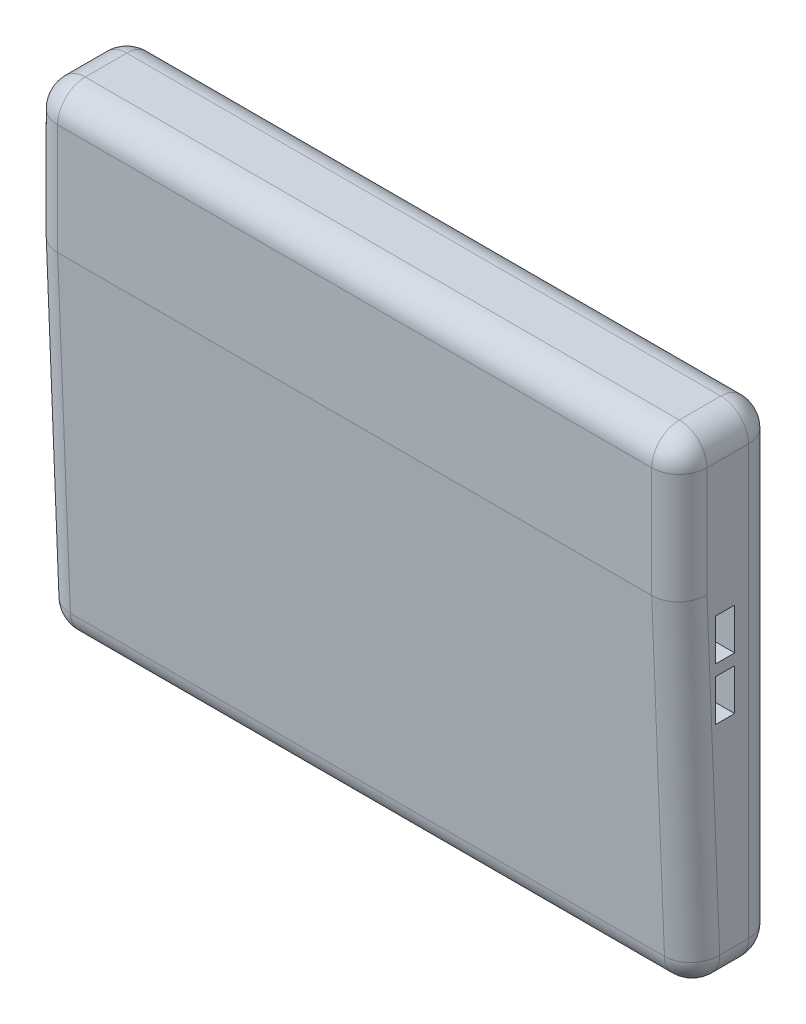
SolidWorks part; units mm, degrees
ref_plane "Plan de face" through (0, 0, 0) normal (0, 0, 1) x (1, 0, 0)
ref_plane "Plan de dessus" through (0, 0, 0) normal (0, 1, 0) x (1, 0, 0)
ref_plane "Plan de droite" through (0, 0, 0) normal (1, 0, 0) x (0, 0, -1)
sketch "Esquisse1" plane through (0, 0, 0) normal (0, 0, 1) x (1, 0, 0)
  line L1 (-32.2034, 29.3169) -> (182.7966, 29.3169)
  line L2 (-42.2034, 19.3169) -> (-42.2034, -135.6831)
  line L3 (-32.2034, -145.6831) -> (182.7966, -145.6831)
  line L4 (192.7966, 19.3169) -> (192.7966, -135.6831)
  arc A0 (-32.2034, 29.3169) -> (-42.2034, 19.3169) centre (-32.2034, 19.3169) ccw
  arc A1 (182.7966, 29.3169) -> (192.7966, 19.3169) centre (182.7966, 19.3169) cw
  arc A2 (-42.2034, -135.6831) -> (-32.2034, -145.6831) centre (-32.2034, -135.6831) ccw
  arc A3 (182.7966, -145.6831) -> (192.7966, -135.6831) centre (182.7966, -135.6831) ccw
  point P6 (-42.2034, 29.3169)
  point P9 (192.7966, 29.3169)
  point P12 (-42.2034, -145.6831)
  dimension "D3" = 10
  dimension "D4" = 10
  dimension "D1" = 235
  dimension "D2" = 175
extrude "Extrusion1" add sketch "Esquisse1" along normal blind 35
sketch "Esquisse5" plane through (192.7966, 0, 0) normal (1, 0, 0) x (0, 0, -1)
  line L0 (-35, -20.6831) -> (-35, -145.6831)
  line L3 (-35, -135.6831) -> (-35, 19.3169) construction
  line L4 (-35, -145.6831) -> (-30, -145.6831)
  line L7 (-30, -145.6831) -> (-35, -20.6831)
  line L8 (-35, 29.3169) -> (0, 29.3169) construction
  line L9 (-35, -145.6831) -> (0, -145.6831) construction
  dimension "D1" = 50
  dimension "D2" = 0
  dimension "D3" = 5
extrude "Extrusion7" cut sketch "Esquisse5" against normal through all
fillet "Congé1" [suppressed] radius 10
fillet "Congé2" radius 10 8 edges at (189.8677, 26.388, 0) (192.7966, -58.1831, 0) (189.8677, -142.7541, 0) (75.2966, -145.6831, 0) (-39.2744, -142.7541, 0) (-42.2034, -58.1831, 0) (-39.2744, 26.388, 0) (75.2966, 29.3169, 0)
sketch "Esquisse2" plane through (192.7966, 0, 0) normal (1, 0, 0) x (0, 0, -1)
  line L0 (-35, 29.3169) -> (-10, 29.3169) construction
  line L1 (-15, -28.6831) -> (-22, -28.6831)
  line L2 (-15, -28.6831) -> (-15, -43.6831)
  line L3 (-15, -43.6831) -> (-22, -43.6831)
  line L4 (-22, -28.6831) -> (-22, -43.6831)
  line L5 (-15, -47.6831) -> (-22, -47.6831)
  line L6 (-15, -47.6831) -> (-15, -62.6831)
  line L7 (-15, -62.6831) -> (-22, -62.6831)
  line L8 (-22, -47.6831) -> (-22, -62.6831)
  line L9 (0, 19.3169) -> (0, -135.6831) construction
  point P12 (0, -58.1831)
  dimension "D1" = 92
  dimension "D2" = 73
  dimension "D3" = 15
  dimension "D4" = 15
  dimension "D5" = 7
  dimension "D6" = 7
  dimension "D7" = 15
  dimension "D8" = 15
extrude "Extrusion2" cut sketch "Esquisse2" against normal blind 15
sketch "Esquisse3" plane through (-42.2034, 0, 0) normal (-1, 0, 0) x (0, 0, 1)
  line L0 (0, 19.3169) -> (0, -135.6831) construction
  line L1 (15, -50.6831) -> (22, -50.6831)
  line L2 (15, -50.6831) -> (15, -65.6831)
  line L3 (15, -65.6831) -> (22, -65.6831)
  line L4 (22, -50.6831) -> (22, -65.6831)
  line L5 (35, 29.3169) -> (10, 29.3169) construction
  line L6 (0, -135.6831) -> (0, 19.3169) construction
  line L7 (12, 7.3169) -> (22, 7.3169)
  line L8 (12, 7.3169) -> (12, -8.6831)
  line L9 (12, -8.6831) -> (22, -8.6831)
  line L10 (22, 7.3169) -> (22, -8.6831)
  dimension "D1" = 15
  dimension "D2" = 7
  dimension "D3" = 15
  dimension "D4" = 80
  dimension "D5" = 16
  dimension "D6" = 10
  dimension "D7" = 12
  dimension "D8" = 22
extrude "Extrusion3" cut sketch "Esquisse3" against normal blind 15
sketch "Esquisse4" plane through (0, 0, 0) normal (0, 0, -1) x (-1, 0, 0)
  line L0 (-75.2966, 19.3169) -> (-75.2966, -135.6831) construction
  line L1 (32.2034, 19.3169) -> (-182.7966, 19.3169) construction
  line L2 (-182.7966, -135.6831) -> (32.2034, -135.6831) construction
  line L3 (-182.7966, -58.1831) -> (32.2034, -58.1831) construction
  line L4 (-182.7966, 19.3169) -> (-182.7966, -135.6831) construction
  line L5 (32.2034, -135.6831) -> (32.2034, 19.3169) construction
  line L6 (-62.2966, -55.1831) -> (-92.2966, -55.1831) construction
  line L7 (-62.9263, -61.2437) -> (-65.7143, -61.2437)
  line L8 (-65.7143, -55.1831) -> (-62.9263, -55.1831)
  line L9 (-62.9263, -55.1831) -> (-62.9263, -61.2437)
  line L10 (-64.8153, -59.8269) -> (-64.8153, -56.5998)
  line L11 (-64.8153, -56.5998) -> (-65.2716, -56.5998)
  line L12 (-65.279, -59.8269) -> (-64.8153, -59.8269)
  line L13 (-68.5978, -59.5809) -> (-71.847, -63.4537)
  line L14 (-71.847, -63.4537) -> (-72.8444, -62.6174)
  line L15 (-72.8444, -62.6174) -> (-70.8103, -60.1934)
  line L16 (-70.8103, -60.1934) -> (-71.5543, -59.5686)
  line L17 (-71.5543, -59.5686) -> (-73.4421, -61.818)
  line L18 (-73.4421, -61.818) -> (-74.3952, -61.0186)
  line L19 (-74.3952, -61.0186) -> (-72.5074, -58.7692)
  line L20 (-72.5074, -58.7692) -> (-73.4298, -57.9944)
  line L21 (-73.4298, -57.9944) -> (-75.523, -60.4885)
  line L22 (-75.523, -60.4885) -> (-76.5819, -59.6006)
  line L23 (-76.5819, -59.6006) -> (-73.2736, -55.6578)
  line L24 (-73.2736, -55.6578) -> (-68.5978, -59.5809)
  line L25 (-77.6607, -61.2437) -> (-79.5497, -61.2437)
  line L26 (-79.5497, -61.2437) -> (-79.5497, -56.6785)
  line L27 (-79.5497, -56.6785) -> (-82.4619, -56.6785)
  line L28 (-82.4619, -56.6785) -> (-82.4619, -55.1831)
  line L29 (-82.4619, -55.1831) -> (-77.6607, -55.1831)
  line L30 (-77.6607, -55.1831) -> (-77.6607, -61.2437)
  line L31 (-83.0444, -61.2437) -> (-84.9334, -61.2437)
  line L32 (-84.9334, -61.2437) -> (-84.9334, -56.6785)
  line L33 (-84.9334, -56.6785) -> (-87.8457, -56.6785)
  line L34 (-87.8457, -56.6785) -> (-87.8457, -55.1831)
  line L35 (-87.8457, -55.1831) -> (-83.0444, -55.1831)
  line L36 (-83.0444, -55.1831) -> (-83.0444, -61.2437)
  circle A0 centre (-75.2966, -58.1831) radius 17.5
  circle A1 centre (-75.2966, -58.1831) radius 15.5
  spline S0 degree 3 poles (-65.7143, -61.2437) (-65.8452, -61.2427) (-66.0367, -61.2382) (-66.285, -61.2145) (-66.4567, -61.1905) (-66.6183, -61.1581) (-66.7704, -61.1204) (-66.9125, -61.0751) (-67.0876, -61.0068) (-67.2891, -60.9018) (-67.5125, -60.7548) (-67.7121, -60.5803) (-67.8896, -60.3832) (-68.0431, -60.1643) (-68.1749, -59.9284) (-68.2853, -59.6761) (-68.3703, -59.4073) (-68.4342, -59.1265) (-68.4982, -58.7357) (-68.513, -58.4359) (-68.5147, -58.2343) knots 0 0 0 0 0.083478 0.122092 0.159074 0.193998 0.227168 0.259007 0.289066 0.346956 0.403527 0.459319 0.515608 0.572271 0.629521 0.687722 0.747595 0.809061 0.87131 1 1 1 1
  spline S1 degree 3 poles (-68.5147, -58.2343) (-68.5139, -58.0813) (-68.5091, -57.8583) (-68.486, -57.5709) (-68.461, -57.3757) (-68.4312, -57.1941) (-68.3929, -57.0257) (-68.3479, -56.8712) (-68.2792, -56.6849) (-68.1766, -56.4712) (-68.0348, -56.2332) (-67.8681, -56.0192) (-67.6833, -55.828) (-67.4841, -55.6624) (-67.2092, -55.4829) (-66.9857, -55.3878) (-66.8322, -55.3479) knots 0 0 0 0 0.127102 0.185195 0.239435 0.290553 0.338059 0.382783 0.424159 0.502921 0.579318 0.653844 0.727786 0.799867 0.868542 1 1 1 1
  spline S2 degree 3 poles (-66.8322, -55.3479) (-66.6388, -55.2959) (-66.2691, -55.2148) (-65.8918, -55.1826) (-65.7143, -55.1831) knots 0 0 0 0 0.530498 1 1 1 1
  spline S3 degree 3 poles (-65.2716, -56.5998) (-65.3614, -56.6013) (-65.4912, -56.6024) (-65.6573, -56.6155) (-65.7662, -56.6309) (-65.8652, -56.6469) (-65.953, -56.6695) (-66.0308, -56.6949) (-66.121, -56.7338) (-66.2216, -56.7984) (-66.3245, -56.9014) (-66.4161, -57.0253) (-66.4792, -57.1468) (-66.521, -57.2582) (-66.549, -57.3562) (-66.5733, -57.4662) (-66.5929, -57.5886) (-66.607, -57.7229) (-66.6227, -57.9261) (-66.6246, -58.085) (-66.6256, -58.1949) knots 0 0 0 0 0.108453 0.156632 0.201086 0.241289 0.277546 0.310419 0.340123 0.396009 0.453417 0.514997 0.581418 0.617918 0.658648 0.704285 0.753927 0.808209 0.867283 1 1 1 1
  spline S4 degree 3 poles (-66.6256, -58.1949) (-66.6252, -58.3393) (-66.6184, -58.5474) (-66.5839, -58.8107) (-66.5519, -58.9817) (-66.5076, -59.1338) (-66.4557, -59.2688) (-66.3913, -59.3838) (-66.3178, -59.4829) (-66.2306, -59.565) (-66.1326, -59.6357) (-66.0212, -59.6951) (-65.8975, -59.744) (-65.7603, -59.7805) (-65.554, -59.8173) (-65.3913, -59.8284) (-65.279, -59.8269) knots 0 0 0 0 0.175309 0.252055 0.321994 0.386215 0.444032 0.497028 0.545671 0.593162 0.641615 0.691909 0.745939 0.802649 0.863818 1 1 1 1
  dimension "D1" = 30
  dimension "D2" = 17
  dimension "D3" = 3
extrude "Extrusion6" cut sketch "Esquisse4" against normal blind 0.1 contours A0 A1 | L36 L35 L34 L33 L32 L31 | L30 L29 L28 L27 L26 L25 | L24 L23 L22 L21 L20 L19 L18 L17 L16 L15 L14 L13 | S2 S1 S0 L7 L9 L8 S4 S3 L11 L10 L12 region at (64.3203, -61.1612, 0) region at (72.3801, -59.3304, 0) region at (79.2667, -57.5843, 0) region at (84.6505, -57.5843, 0) region at (92.3017, -58.1831, 0)
fillet "Congé3" radius 10 10 edges at (192.7966, -0.6831, 35) (189.8677, 26.388, 35) (75.2966, 29.3169, 35) (-39.2744, 26.388, 35) (-42.2034, -0.6831, 35) (-42.2034, -78.1831, 32.7) (-39.2744, -142.7541, 30.1172) (75.2966, -145.6831, 30) (189.8677, -142.7541, 30.1172) (192.7966, -78.1831, 32.7)
